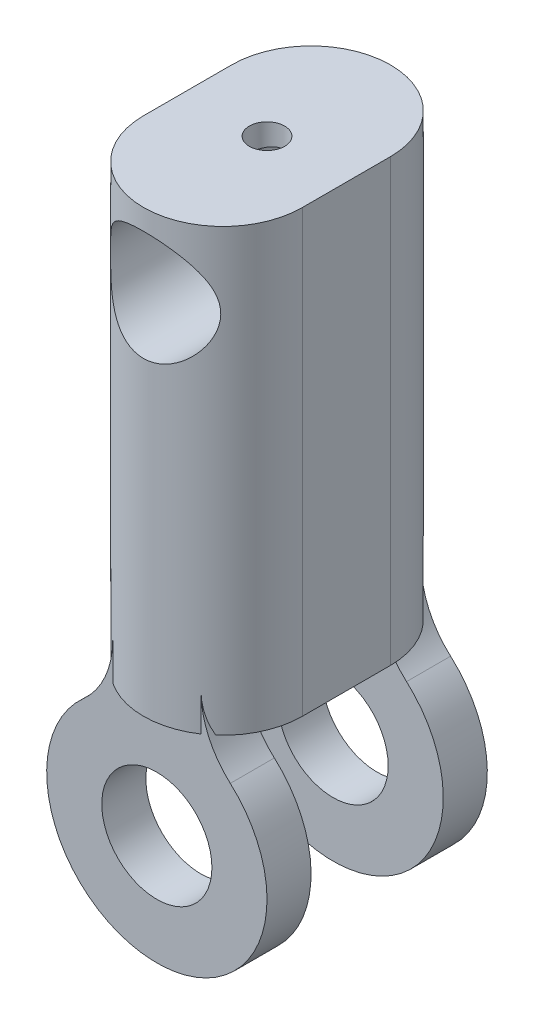
SolidWorks part; units mm, degrees
ref_plane "Front Plane" through (0, 0, 0) normal (0, 0, 1) x (1, 0, 0)
ref_plane "Top Plane" through (0, 0, 0) normal (0, 1, 0) x (1, 0, 0)
ref_plane "Right Plane" through (0, 0, 0) normal (1, 0, 0) x (0, 0, -1)
sketch "Sketch1" plane through (0, 0, 0) normal (0, 0, 1) x (1, 0, 0)
  line L1 (5, 18.4564) -> (-5, 18.4564)
  line L2 (5, 18.4564) -> (5, 16.7705)
  line L4 (-5, 18.4564) -> (-5, 16.7705)
  arc A0 (-8.3333, 9.3169) -> (8.3333, 9.3169) centre (0, 0) ccw
  circle A1 centre (0, 0) radius 6.25
  arc A3 (-5, 16.7705) -> (-8.3333, 9.3169) centre (-15, 16.7705) cw
  arc A4 (8.3333, 9.3169) -> (5, 16.7705) centre (15, 16.7705) cw
  point P1 (0, 18.4564)
  point P4 (0, 12.7784)
  point P16 (5, 11.4564)
  dimension "D1" = 25
  dimension "D2" = 12.5
  dimension "D5" = 10
  dimension "D3" = 10
  dimension "D4" = 7
extrude "Boss-Extrude1" add sketch "Sketch1" along normal blind 5 from offset 7.5 contours L4 A0 L2 L1 A1 region at (4.6021, 17.6135, 0)
extrude "Boss-Extrude2" add sketch "Sketch1<2>" against normal blind 5 from offset 7.5 separate body contours L4 A0 L2 L1 A1 region at (4.6021, 17.6135, 0) offset against normal yes
sketch "Sketch1<2>" plane through (0, 0, 0) normal (0, 0, 1) x (1, 0, 0) same geometry as "Sketch1"
sketch "Sketch2" plane through (0, 0, 0) normal (0, 1, 0) x (1, 0, 0)
  line L0 (0, 5) -> (0, -5) construction
  line L1 (9.0139, 5) -> (9.0139, -5)
  line L2 (-9.0139, 5) -> (-9.0139, -5)
  arc A0 (9.0139, 5) -> (-9.0139, 5) centre (0, 5) ccw
  arc A1 (-9.0139, -5) -> (9.0139, -5) centre (0, -5) ccw
  point P2 (0, 0)
  dimension "D2" = 10
extrude "Boss-Extrude3" add sketch "Sketch2" along normal blind 50 from offset 12.5
sketch "Sketch3" plane through (0, 12.5, 0) normal (0, -1, 0) x (1, 0, 0)
  line L0 (-9.0139, 0) -> (9.0139, 0) construction
  line L1 (-9.0139, -5) -> (-9.0139, 5) construction
  line L2 (9.0139, 5) -> (9.0139, -5) construction
  line L3 (0, -7.5) -> (0, 7.5) construction
  line L4 (-5.9577, -7.5) -> (5.9577, -7.5) construction
  line L5 (5.9577, 7.5) -> (-5.9577, 7.5) construction
  circle A0 centre (0, 0) radius 2
  dimension "D1" = 4
  dimension "D2" = 0
extrude "Cut-Extrude1" cut sketch "Sketch3" against normal blind 56
sketch "Sketch4" plane through (0, 0, 0) normal (0, 0, 1) x (1, 0, 0)
  circle A0 centre (0, 53.9159) radius 6.25
  dimension "D1" = 12.5
extrude "Cut-Extrude2" cut sketch "Sketch4" against normal blind 29 and the other way blind 47
